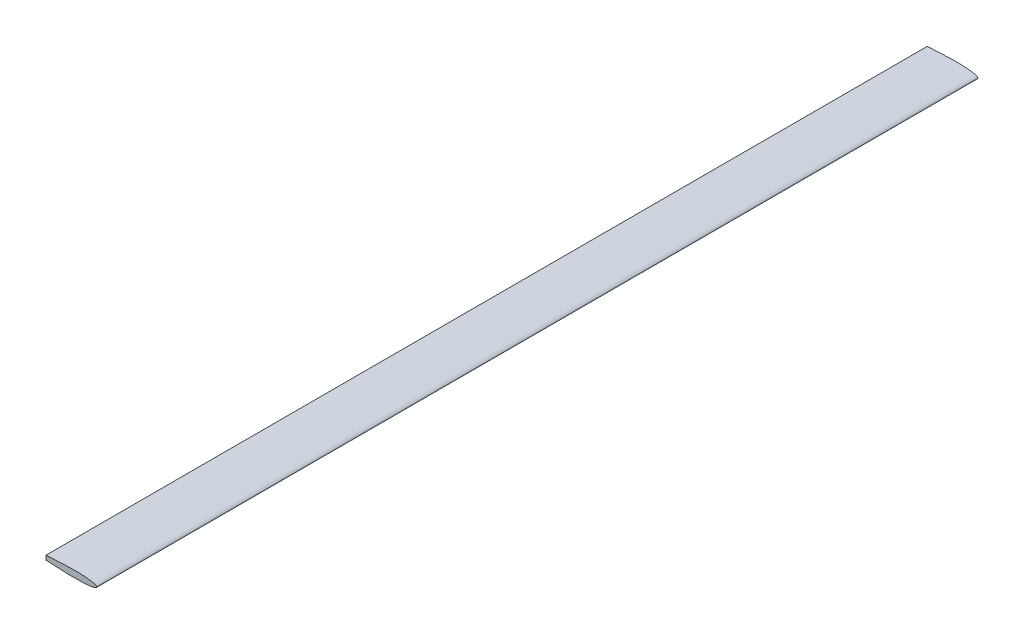
SolidWorks part; units mm, degrees
ref_plane "Front Plane" through (0, 0, 0) normal (0, 0, 1) x (1, 0, 0)
ref_plane "Top Plane" through (0, 0, 0) normal (0, 1, 0) x (1, 0, 0)
ref_plane "Right Plane" through (0, 0, 0) normal (1, 0, 0) x (0, 0, -1)
sketch "Sketch1" plane through (0, 0, 0) normal (0, 0, 1) x (1, 0, 0)
  line L0 (-51.4087, 2.1838) -> (-51.4087, -2.1838)
  spline S0 degree 3 poles (-51.4087, 2.1838) (-50.7663, 2.2297) (-48.8506, 2.3667) (-45.6317, 2.5741) (-41.7381, 2.8043) (-37.8013, 3.0073) (-33.8645, 3.1769) (-29.9707, 3.3054) (-26.1625, 3.386) (-22.4818, 3.4128) (-18.9687, 3.3809) (-15.6616, 3.2876) (-12.5969, 3.132) (-9.8077, 2.9153) (-7.3247, 2.6409) (-5.174, 2.3146) (-3.379, 1.9416) (-1.953, 1.5346) (-0.9111, 1.0878) (-0.2171, 0.6262) (0.0897, 0) (-0.2171, -0.6262) (-0.9111, -1.0878) (-1.953, -1.5346) (-3.379, -1.9416) (-5.174, -2.3146) (-7.3247, -2.6409) (-9.8077, -2.9153) (-12.5969, -3.132) (-15.6616, -3.2876) (-18.9687, -3.3809) (-22.4818, -3.4128) (-26.1625, -3.386) (-29.9707, -3.3054) (-33.8645, -3.1769) (-37.8013, -3.0073) (-41.7381, -2.8043) (-45.6317, -2.5741) (-48.8506, -2.3667) (-50.7663, -2.2297) (-51.4087, -2.1838) knots 0 0 0 0 0.018499 0.055171 0.092655 0.130539 0.168407 0.205846 0.242449 0.277819 0.311577 0.343364 0.372846 0.399719 0.423712 0.444594 0.46218 0.476354 0.487106 0.494669 0.5 0.505331 0.512894 0.523646 0.53782 0.555406 0.576288 0.600281 0.627154 0.656636 0.688423 0.722181 0.757551 0.794154 0.831593 0.869461 0.907345 0.944829 0.981501 1 1 1 1
extrude "Boss-Extrude1" add sketch "Sketch1" along normal mid plane 892.8
